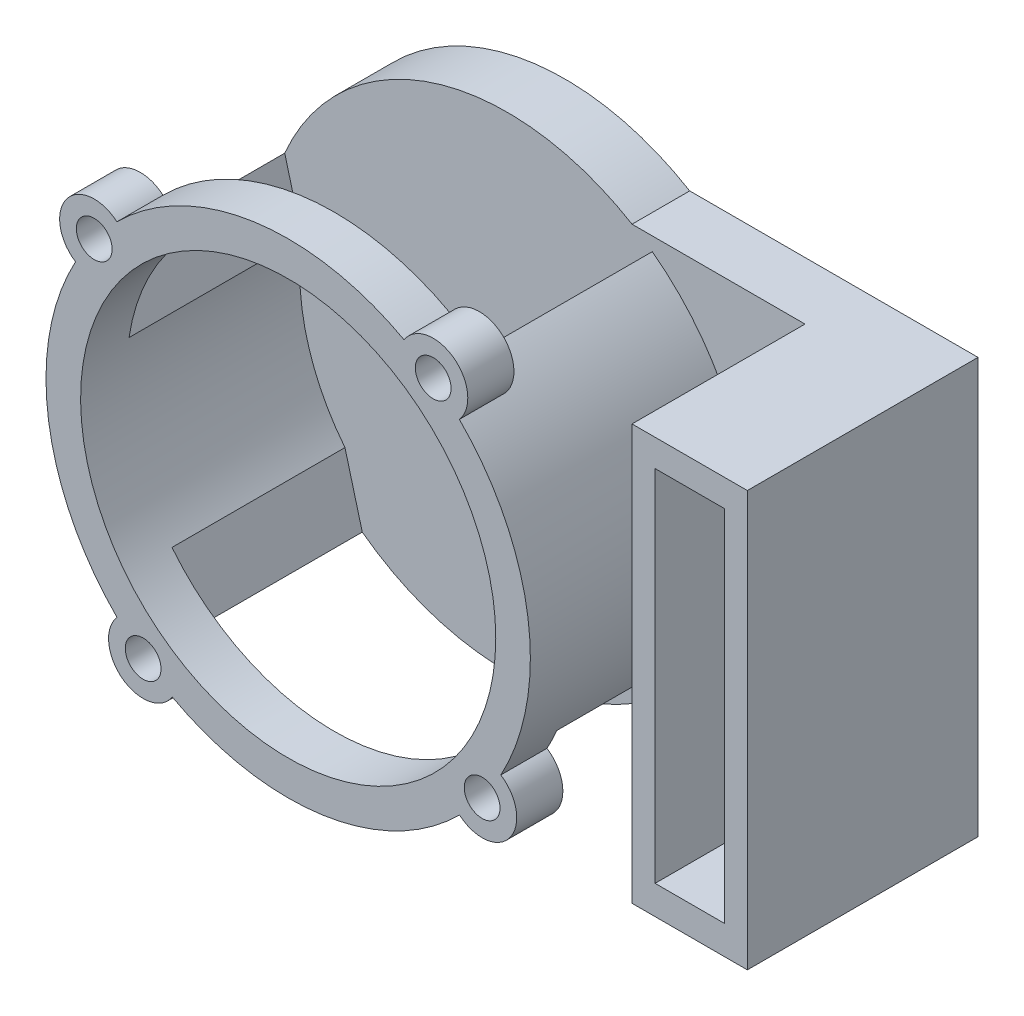
SolidWorks part; units mm, degrees
ref_plane "Piano frontale" through (0, 0, 0) normal (0, 0, 1) x (1, 0, 0)
ref_plane "Piano superiore" through (0, 0, 0) normal (0, 1, 0) x (1, 0, 0)
ref_plane "Piano destro" through (0, 0, 0) normal (1, 0, 0) x (0, 0, -1)
sketch "Schizzo1" plane through (0, 0, 0) normal (0, 0, 1) x (1, 0, 0)
  line L0 (22.3655, 11.6094) -> (47.3655, 11.6094) construction
  line L1 (22.3655, -24.3906) -> (47.3655, -24.3906)
  line L2 (47.3655, -24.3906) -> (47.3655, 11.6094)
  line L3 (47.3655, 11.6094) -> (22.3655, 11.6094)
  arc A2 (22.3655, 11.6094) -> (22.3655, -24.3906) centre (11.5488, -6.3906) ccw
  dimension "D1" = 25
  dimension "D3" = 42
  dimension "D2" = 36
extrude "Estrusione-Estrusione1" add sketch "Schizzo1" along normal mid plane 5
sketch "Schizzo2" plane through (0, 0, 2.5) normal (0, 0, 1) x (1, 0, 0)
  line L1 (37.3655, 11.6094) -> (47.3655, 11.6094)
  line L2 (37.3655, 11.6094) -> (37.3655, -24.3906)
  line L3 (37.3655, -24.3906) -> (47.3655, -24.3906)
  line L4 (47.3655, 11.6094) -> (47.3655, -24.3906)
  line L5 (37.3655, 11.6094) -> (47.3655, -24.3906) construction
  line L6 (37.3655, -24.3906) -> (47.3655, 11.6094) construction
  point P0 (42.3655, -6.3906)
  dimension "D1" = 10
extrude "Estrusione-Estrusione2" add sketch "Schizzo2" along normal blind 15
sketch "Schizzo3" plane through (0, 0, 17.5) normal (0, 0, 1) x (1, 0, 0)
  line L1 (39.3655, 9.2594) -> (45.3655, 9.2594)
  line L2 (39.3655, 9.2594) -> (39.3655, -21.8906)
  line L3 (39.3655, -21.8906) -> (45.3655, -21.8906)
  line L4 (45.3655, 9.2594) -> (45.3655, -21.8906)
  line L5 (39.3655, 9.2594) -> (45.3655, -21.8906) construction
  line L6 (39.3655, -21.8906) -> (45.3655, 9.2594) construction
  line L7 (47.3655, -24.3906) -> (47.3655, 11.6094) construction
  line L8 (37.3655, -24.3906) -> (47.3655, -24.3906) construction
  point P0 (42.3655, -6.3156)
  dimension "D1" = 6
  dimension "D2" = 2
  dimension "D3" = 31.15
  dimension "D4" = 2.5
extrude "Taglio-Estrusione1" cut sketch "Schizzo3" against normal blind 13
sketch "Schizzo5" plane through (0, 0, 2.5) normal (0, 0, 1) x (1, 0, 0)
  line L0 (37.3655, -6.3906) -> (-9.4512, -6.3906) construction
  line L1 (37.3655, 11.6094) -> (37.3655, -24.3906) construction
  line L3 (11.5488, -27.3906) -> (11.5488, 14.6094) construction
  arc A0 (22.3655, 11.6094) -> (22.3655, -24.3906) centre (11.5488, -6.3906) ccw construction
  circle A1 centre (11.5488, -6.3906) radius 21
extrude "Estrusione-Sottile1" add sketch "Schizzo5" along normal blind 19 thin thin type one direction reverse wall 3
sketch "Schizzo7" plane through (0, 0, 4.5) normal (0, 0, 1) x (1, 0, 0)
  line L0 (39.3655, -21.8906) -> (45.3655, -20.283) construction
  line L1 (45.3655, -21.8906) -> (45.3655, 9.2594) construction
  line L2 (39.3655, -21.8906) -> (38.3708, -18.1785) construction
  line L3 (39.3655, -21.8906) -> (45.3655, -21.8906) construction
  line L4 (45.3655, -21.8906) -> (39.3655, -21.8906) construction
  dimension "D1" = 15
ref_plane "Piano1" through (-3.0639, 11.4347, 0) normal (-0.2588, 0.9659, 0) x (0.9659, 0.2588, 0)
sketch "Schizzo8" plane through (-3.0639, 11.4347, 0) normal (-0.2588, 0.9659, 0) x (0.9659, 0.2588, 0)
  line L6 (9.5013, -21.5) -> (9.5013, 2.5) construction
  line L7 (-11.4987, -21.5) -> (30.5013, -21.5) construction
  line L8 (24.6081, 2.5) -> (-11.4987, 2.5) construction
  line L9 (-6.9987, -17.5) -> (26.0013, -17.5)
  line L10 (26.0013, -17.5) -> (26.0013, -2.5)
  line L11 (15.2906, -2.5) -> (30.5013, -2.5) construction
  line L12 (26.0013, -2.5) -> (-6.9987, -2.5)
  line L13 (-6.9987, -2.5) -> (-6.9987, -17.5)
  dimension "D1" = 16.5
  dimension "D2" = 33
  dimension "D3" = 4
extrude "Taglio-Estrusione2" cut sketch "Schizzo8" against normal through all
sketch "Schizzo10" plane through (0, 0, 21.5) normal (0, 0, 1) x (1, 0, 0)
  line L0 (-1.0268, -23.2089) -> (24.1245, 10.4276) construction
  line L2 (28.3671, -18.9663) -> (-5.2694, 6.185) construction
  circle A0 centre (11.5488, -6.3906) radius 21 construction
  circle A2 centre (-5.2694, 6.185) radius 3
  circle A3 centre (24.1245, 10.4276) radius 3
  circle A4 centre (28.3671, -18.9663) radius 3
  circle A5 centre (-1.0268, -23.2089) radius 3
  dimension "D2" = 6
  dimension "D3" = 6
  dimension "D4" = 6
  dimension "D5" = 6
  dimension "D1" = 42
extrude "Estrusione-Estrusione3" add sketch "Schizzo10" against normal blind 4
hole_wizard "Foro per Vite M2.5-1" positions "Schizzo3D2" profile "Schizzo13" hole size "M2.5" standard "ISO"
sketch3d "Schizzo3D2"
  point P1 (24.1245, 10.4276, 21.5)
  point P4 (28.3671, -18.9663, 21.5)
  point P7 (-1.0268, -23.2089, 21.5)
  point P10 (-5.2694, 6.185, 21.5)
sketch "Schizzo13" plane through (24.1245, 10.4276, 21.5) normal (1, 0, 0) x (0, -1, 0)
  line L0 (0, 0) -> (0, 3.9313)
  line L1 (0, 3.9313) -> (1.55, 3)
  line L2 (1.55, 3) -> (1.55, 0)
  line L5 (1.55, 0) -> (0, 0)
  line L10 (0, 3.9313) -> (-1.55, 3) construction
  line L11 (0, -6.35) -> (0, 107.95) construction
  dimension "Hole Dia." = 3.1
  dimension "Hole Depth" = 3
  dimension "Drill Angle" = 118
